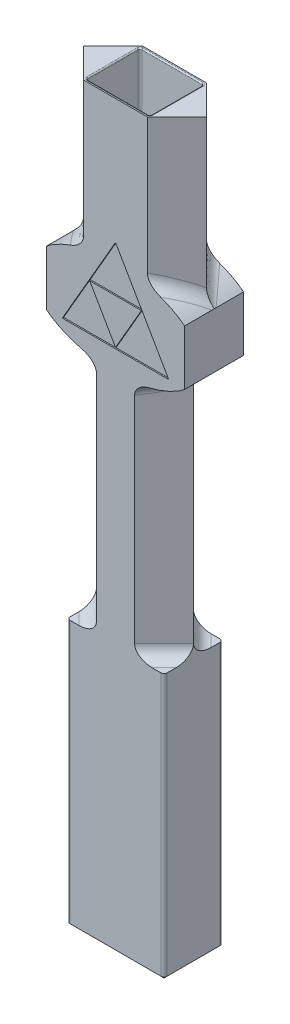
SolidWorks part; units mm, degrees
material "Plain Carbon Steel"
ref_plane "Front Plane" through (0, 0, 0) normal (0, 0, 1) x (1, 0, 0)
ref_plane "Top Plane" through (0, 0, 0) normal (0, 1, 0) x (1, 0, 0)
ref_plane "Right Plane" through (0, 0, 0) normal (1, 0, 0) x (0, 0, -1)
sketch "Sketch1" plane through (0, 0, 0) normal (0, 1, 0) x (1, 0, 0)
  line L1 (-10.287, -6.096) -> (10.287, -6.096)
  line L2 (-10.287, -6.096) -> (-10.287, 6.096)
  line L3 (-10.287, 6.096) -> (10.287, 6.096)
  line L4 (10.287, -6.096) -> (10.287, 6.096)
  line L5 (-10.287, -6.096) -> (10.287, 6.096) construction
  line L6 (-10.287, 6.096) -> (10.287, -6.096) construction
  point P0 (0, 0)
  dimension "D1" = 12.192
  dimension "D2" = 20.574
extrude "Boss-Extrude1" add sketch "Sketch1" along normal blind 50.8
chamfer "Chamfer1" distance 6.35 angle 45 4 edges at (10.287, 25.4, -6.096) (10.287, 25.4, 6.096) (-10.287, 25.4, -6.096) (-10.287, 25.4, 6.096)
sketch "Sketch3" plane through (0, 0, 0) normal (0, -1, 0) x (1, 0, 0)
  line L0 (-3.937, 6.096) -> (3.937, 6.096) construction
  line L1 (-10.033, -6.096) -> (10.033, -6.096)
  line L2 (-10.033, -6.096) -> (-10.033, 6.096)
  line L3 (-10.033, 6.096) -> (10.033, 6.096)
  line L4 (10.033, -6.096) -> (10.033, 6.096)
  line L5 (-10.033, -6.096) -> (10.033, 6.096) construction
  line L6 (-10.033, 6.096) -> (10.033, -6.096) construction
  point P0 (0, 0)
extrude "Boss-Extrude3" add sketch "Sketch3" along normal blind 54.9656
fillet "Fillet1" radius 0.635 4 edges at (10.033, -27.4828, 6.096) (10.033, -27.4828, -6.096) (-10.033, -27.4828, -6.096) (-10.033, -27.4828, 6.096)
fillet "Fillet14" radius 2.54 2 edges at (6.985, 0, 3.048) (-6.985, 0, 3.048)
fillet "Fillet15" radius 2.54 2 edges at (-6.985, 0, -3.048) (6.985, 0, -3.048)
sketch "Sketch4" plane through (0, 0, 0) normal (0, 0, 1) x (1, 0, 0)
  ellipse E0 centre (0, 58.8933) end of major axis (-17.4625, 58.8933) minor radius 9.8883
  dimension "D1" = 34.925
  dimension "D2" = 19.7766
extrude "Boss-Extrude4" add sketch "Sketch4" along normal mid plane 12.192
fillet "Fillet19" radius 2.54 4 edges at (6.9978, 49.8337, -3.0352) (7.0227, 49.8399, 3.0103) (-7.0227, 49.8399, -3.0103) (-6.9978, 49.8337, 3.0352)
ref_plane "Plane1" through (0, 68.961, 0) normal (0, 1, 0) x (1, 0, 0)
sketch "Sketch5" plane through (0, 68.961, 0) normal (0, 1, 0) x (1, 0, 0)
  line L0 (17.4625, 6.096) -> (17.4625, -6.096)
  line L1 (17.4625, -6.096) -> (14.2875, -6.096)
  line L2 (-17.4625, -6.096) -> (17.4625, -6.096) construction
  line L3 (14.2875, -6.096) -> (14.2875, 6.096)
  line L4 (17.4625, 6.096) -> (-17.4625, 6.096) construction
  line L5 (14.2875, 6.096) -> (17.4625, 6.096)
  dimension "D1" = 3.175
extrude "Cut-Extrude1" cut sketch "Sketch5" against normal through all both and the other way through all
mirror "Mirror1" about plane through (0, 0, 0) normal (1, 0, 0) of "Cut-Extrude1"
sketch "Sketch6" plane through (0, 68.961, 0) normal (0, 1, 0) x (1, 0, 0)
  line L0 (-12.7, 0) -> (-6.604, 6.096)
  line L1 (14.2875, 6.096) -> (-14.2875, 6.096) construction
  line L2 (-6.604, 6.096) -> (6.604, 6.096)
  line L3 (6.604, 6.096) -> (12.7, 0)
  line L4 (12.7, 0) -> (6.604, -6.096)
  line L5 (6.604, -6.096) -> (-6.604, -6.096)
  line L6 (-6.604, -6.096) -> (-12.7, 0)
  line L7 (-14.2875, -6.096) -> (14.2875, -6.096) construction
  point P10 (0, 6.096)
  dimension "D1" = 25.4
extrude "Boss-Extrude5" add sketch "Sketch6" along normal blind 3.81 and the other way up to next
fillet "Fillet22" radius 2.54 4 edges at (-9.6819, 67.1226, -3.0181) (-9.7248, 67.1064, 2.9752) (9.7248, 67.1064, -2.9752) (9.6819, 67.1226, 3.0181)
sketch "Sketch8" plane through (0, 72.771, 0) normal (0, 1, 0) x (1, 0, 0)
  line L0 (-12.7, 0) -> (-6.604, 6.096)
  line L1 (-6.604, 6.096) -> (6.604, 6.096)
  line L2 (6.604, 6.096) -> (12.7, 0)
  line L3 (12.7, 0) -> (6.604, -6.096)
  line L4 (6.604, -6.096) -> (-6.604, -6.096)
  line L5 (-6.604, -6.096) -> (-12.7, 0)
  dimension "D1" = 25.4
  dimension "D2" = 12.192
extrude "Boss-Extrude7" add sketch "Sketch8" along normal blind 25.4
sketch "Sketch9" plane through (0, 98.171, 0) normal (0, 1, 0) x (1, 0, 0)
  circle A0 centre (0, 0) radius 4.7625
  dimension "D1" = 9.525
extrude "Cut-Extrude2" cut sketch "Sketch9" against normal through all
sketch "Sketch10" plane through (0, 98.171, 0) normal (0, 1, 0) x (1, 0, 0)
  line L0 (6.604, 6.096) -> (-6.604, 6.096) construction
  line L1 (-6.604, -5.588) -> (6.604, -5.588)
  line L2 (-6.604, -5.588) -> (-6.604, 5.588)
  line L3 (-6.604, 5.588) -> (6.604, 5.588)
  line L4 (6.604, -5.588) -> (6.604, 5.588)
  line L5 (-6.604, -5.588) -> (6.604, 5.588) construction
  line L6 (-6.604, 5.588) -> (6.604, -5.588) construction
  point P0 (0, 0)
  dimension "D1" = 0.508
  dimension "D2" = 13.208
  dimension "D3" = 11.176
extrude "Cut-Extrude3" cut sketch "Sketch10" against normal blind 12.7
fillet "Fillet23" radius 0.381 4 edges at (-6.604, 85.471, 0) (0, 85.471, 5.588) (6.604, 85.471, 0) (0, 85.471, -5.588)
chamfer "Chamfer2" distance 0.635 angle 45 8 edges at (9.847, -54.9656, -5.91) (10.033, -54.9656, 0) (9.847, -54.9656, 5.91) (0, -54.9656, 6.096) (-9.847, -54.9656, 5.91) (-10.033, -54.9656, 0) (-9.847, -54.9656, -5.91) (0, -54.9656, -6.096)
fillet "Fillet25" radius 0.381 8 edges at (6.4924, 85.5826, 5.4764) (-6.4924, 85.5826, 5.4764) (-6.4924, 85.5826, -5.4764) (6.4924, 85.5826, -5.4764) (6.604, 92.0115, 5.588) (-6.604, 92.0115, 5.588) (-6.604, 92.0115, -5.588) (6.604, 92.0115, -5.588)
sketch "Sketch11" plane through (0, 0, 6.096) normal (0, 0, 1) x (1, 0, 0)
  line L0 (0, 72.39) -> (-10.9985, 53.34)
  line L1 (-10.9985, 53.34) -> (10.9985, 53.34)
  line L2 (10.9985, 53.34) -> (0, 72.39)
  line L6 (-5.3526, 62.865) -> (5.3526, 62.865)
  line L7 (5.3526, 62.865) -> (0, 53.594)
  line L8 (0, 53.594) -> (-5.3526, 62.865)
  point P8 (5.4993, 62.865)
  point P9 (-5.4993, 62.865)
  point P12 (0, 53.34)
  dimension "D1" = 53.34
  dimension "D2" = 19.05
  dimension "D3" = 0.127
extrude "Cut-Extrude8" cut sketch "Sketch11" against normal blind 0.254
mirror "Mirror2" about plane through (0, 0, 0) normal (0, 0, 1) of "Cut-Extrude8"
fillet "Fillet27" radius 0.254 8 edges at (6.4924, 98.171, 5.4764) (0, 98.171, 5.588) (-6.4924, 98.171, 5.4764) (-6.604, 98.171, 0) (-6.4924, 98.171, -5.4764) (0, 98.171, -5.588) (6.4924, 98.171, -5.4764) (6.604, 98.171, 0)
